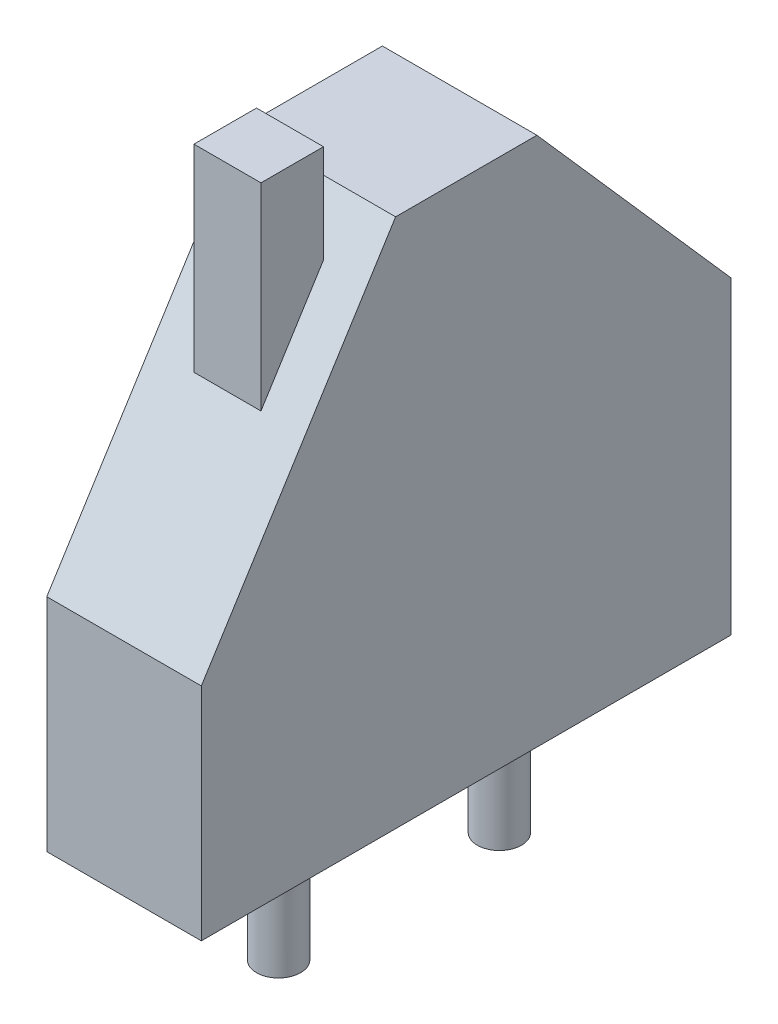
SolidWorks part; units mm, degrees
ref_plane "前视基准面" through (0, 0, 0) normal (0, 0, 1) x (1, 0, 0)
ref_plane "上视基准面" through (0, 0, 0) normal (0, 1, 0) x (1, 0, 0)
ref_plane "右视基准面" through (0, 0, 0) normal (1, 0, 0) x (0, 0, -1)
sketch "草图1" plane through (0, 0, 0) normal (0, 1, 0) x (1, 0, 0)
  line L0 (-45.7415, 0) -> (52.4503, 0) construction
  line L1 (-1.75, 6) -> (1.75, 6)
  line L2 (-1.75, 6) -> (-1.75, -6)
  line L3 (-1.75, -6) -> (1.75, -6)
  line L4 (1.75, 6) -> (1.75, -6)
  line L5 (0, 37.5081) -> (0, -35.6784) construction
  dimension "D1" = 3.5
  dimension "D2" = 12
extrude "拉伸1" add sketch "草图1" along normal blind 12
sketch "草图2" plane through (0, 0, 0) normal (0, -1, 0) x (1, 0, 0)
  line L0 (0, -7.7319) -> (0, 7.3875) construction
  line L1 (3.4268, 0) -> (-3.9951, 0) construction
  circle A0 centre (0, 2.5) radius 0.5
  circle A1 centre (0, -2.5) radius 0.5
  dimension "D2" = 1
  dimension "D3" = 1
  dimension "D1" = 2.5
  dimension "D4" = 2.5
extrude "拉伸2" add sketch "草图2" along normal blind 3
sketch "草图3" plane through (1.75, 0, 0) normal (1, 0, 0) x (0, 0, -1)
  line L0 (0, -1.7938) -> (0, 18.4087) construction
  line L1 (-1.6, 12) -> (-6, 5)
  line L2 (-6, 12) -> (6, 12) construction
  line L3 (-6, 12) -> (-6, 0) construction
  line L4 (1.6, 12) -> (6, 7)
  line L5 (6, 12) -> (6, 0) construction
  line L6 (-6, 5) -> (-6, 12)
  line L7 (-6, 12) -> (-1.6, 12)
  line L8 (6, 7) -> (6, 12)
  line L9 (6, 12) -> (1.6, 12)
  dimension "D1" = 1.6
  dimension "D2" = 7
  dimension "D3" = 1.6
  dimension "D4" = 5
extrude "切除-拉伸1" cut sketch "草图3" against normal blind 5
sketch "草图4" plane through (0, 0, 0) normal (0, -1, 0) x (1, 0, 0)
  line L0 (0, -1.0391) -> (0, 5.0529) construction
  line L1 (-0.7586, 3.6582) -> (0.7586, 3.6582)
  line L2 (-0.7586, 3.6582) -> (-0.7586, 2.2421)
  line L3 (-0.7586, 2.2421) -> (0.7586, 2.2421)
  line L4 (0.7586, 3.6582) -> (0.7586, 2.2421)
extrude "凸台-拉伸1" add sketch "草图4" against normal blind 13.2
sketch "草图5" plane through (0, 0, -6) normal (0, 0, -1) x (-1, 0, 0)
  line L0 (0, -0.7236) -> (0, 5.0678) construction
  line L1 (-0.7586, 3.319) -> (0.7586, 3.319)
  line L2 (-0.7586, 3.319) -> (-0.7586, 2.0926)
  line L3 (-0.7586, 2.0926) -> (0.7586, 2.0926)
  line L4 (0.7586, 3.319) -> (0.7586, 2.0926)
extrude "切除-拉伸2" cut sketch "草图5" against normal blind 2
chamfer "倒角1" distance 0.5 angle 45 4 edges at (-0.7586, 2.7058, -6) (0, 3.319, -6) (0.7586, 2.7058, -6) (0, 2.0926, -6)
